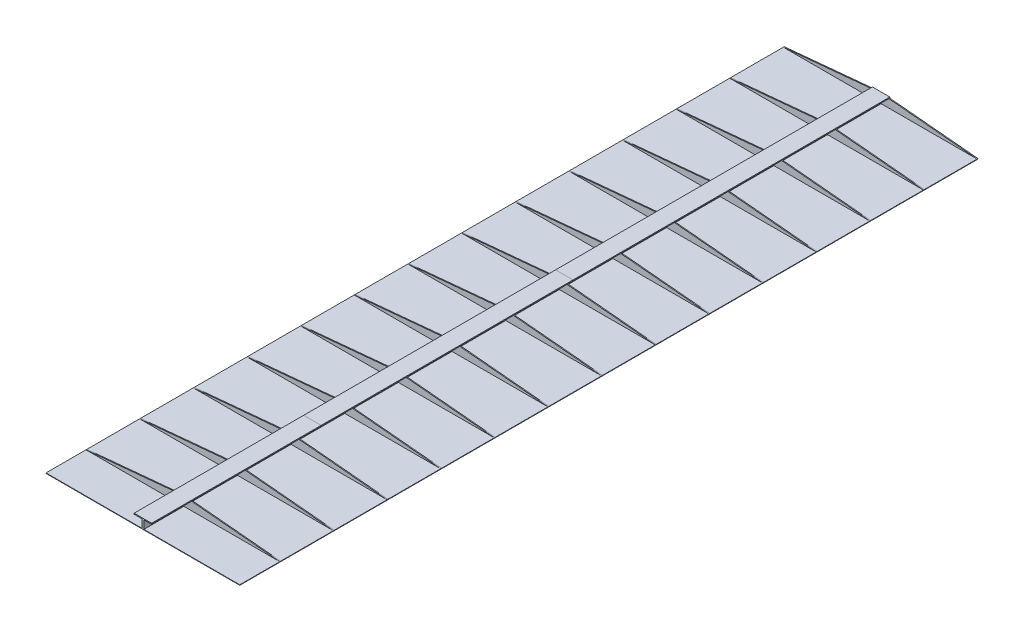
SolidWorks part; units mm, degrees
material "6061-T6 (SS)"
ref_plane "Front Plane" through (0, 0, 0) normal (0, 0, 1) x (1, 0, 0)
ref_plane "Top Plane" through (0, 0, 0) normal (0, 1, 0) x (1, 0, 0)
ref_plane "Right Plane" through (0, 0, 0) normal (1, 0, 0) x (0, 0, -1)
sketch "Sketch1" plane through (0, 0, 0) normal (0, 0, 1) x (1, 0, 0)
  line L0 (-90, 95) -> (90, 95)
  line L1 (90, 95) -> (90, 0)
  line L2 (90, 0) -> (1000, 0)
  line L3 (1000, 0) -> (1000, -5)
  line L4 (1000, -5) -> (-1000, -5)
  line L5 (-1000, -5) -> (-1000, 0)
  line L6 (-1000, 0) -> (-90, 0)
  line L7 (-90, 0) -> (-90, 95)
  dimension "D1" = 100
  dimension "D2" = 180
  dimension "D3" = 90
  dimension "D4" = 5
  dimension "D5" = 2000
extrude "Boss-Extrude1" add sketch "Sketch1" against normal blind 7620
sketch "Sketch7" plane through (0, 0, -7620) normal (0, 0, -1) x (-1, 0, 0)
  line L0 (-90, 0) -> (-90, 95) construction
  line L1 (-90, 85) -> (-10, 85)
  line L2 (-90, 85) -> (-90, 0)
  line L3 (-90, 0) -> (-10, 0)
  line L4 (-10, 85) -> (-10, 0)
  line L5 (-90, 95) -> (90, 95) construction
  line L6 (1000, -5) -> (-1000, -5) construction
  line L7 (90, 95) -> (90, 0) construction
  line L8 (90, 85) -> (10, 85)
  line L9 (90, 85) -> (90, 0)
  line L10 (90, 0) -> (10, 0)
  line L11 (10, 85) -> (10, 0)
  dimension "D1" = 10
  dimension "D2" = 5
  dimension "D3" = 20
extrude "Cut-Extrude3" cut sketch "Sketch7" against normal through all
sketch "Sketch8" plane through (0, 0, -7620) normal (0, 0, -1) x (-1, 0, 0)
  line L0 (-10, 0) -> (-10, 85)
  line L1 (-10, 85) -> (-90, 85)
  line L2 (-90, 85) -> (-1000, 0)
  line L3 (-1000, 0) -> (-10, 0)
extrude "Boss-Extrude3" add sketch "Sketch8" against normal blind 9.525
pattern_linear "LPattern2" count 14 spacing 553.68 along (0, 0, 1) of "Boss-Extrude3"
mirror "Mirror2" about plane through (0, 0, 0) normal (1, 0, 0) of "LPattern2"
sketch "Sketch9" plane through (0, 95, 0) normal (0, 1, 0) x (1, 0, 0)
  line L0 (90, 7620) -> (90, 0) construction
  line L1 (90, 1750) -> (-90, 1750)
  line L2 (90, 1750) -> (90, 4350)
  line L3 (90, 4350) -> (-90, 4350)
  line L4 (-90, 1750) -> (-90, 4350)
  line L5 (-90, 7620) -> (-90, 0) construction
  line L6 (90, 0) -> (-90, 0) construction
  dimension "D1" = 2600
  dimension "D2" = 1750
split line "Split Line2"
